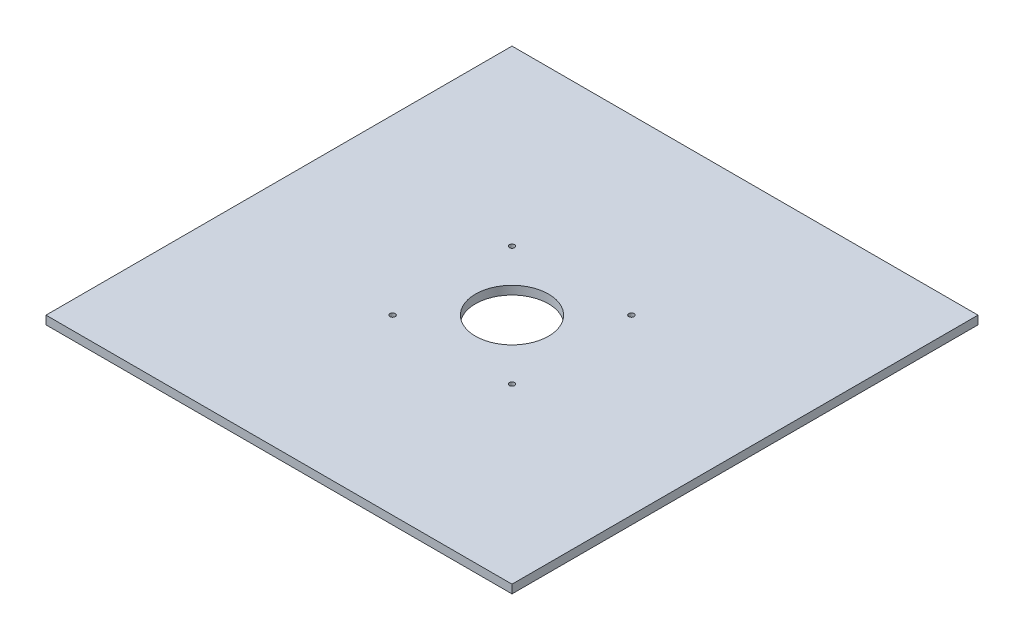
SolidWorks part; units mm, degrees
ref_plane "Front Plane" through (0, 0, 0) normal (0, 0, 1) x (1, 0, 0)
ref_plane "Top Plane" through (0, 0, 0) normal (0, 1, 0) x (1, 0, 0)
ref_plane "Right Plane" through (0, 0, 0) normal (1, 0, 0) x (0, 0, -1)
sketch "Sketch1" plane through (0, 0, 0) normal (0, 1, 0) x (1, 0, 0)
  line L1 (-175, -175) -> (175, -175)
  line L2 (-175, -175) -> (-175, 175)
  line L3 (-175, 175) -> (175, 175)
  line L4 (175, -175) -> (175, 175)
  line L5 (-175, -175) -> (175, 175) construction
  line L6 (-175, 175) -> (175, -175) construction
  point P0 (0, 0)
  dimension "D1" = 350
  dimension "D2" = 350
extrude "Boss-Extrude1" add sketch "Sketch1" along normal blind 6.35
sketch "Sketch2" plane through (0, 6.35, 0) normal (0, 1, 0) x (1, 0, 0)
  line L1 (-44.8437, -44.8437) -> (44.8437, -44.8437) construction
  line L2 (-44.8437, -44.8437) -> (-44.8437, 44.8437) construction
  line L3 (-44.8437, 44.8437) -> (44.8437, 44.8437) construction
  line L4 (44.8437, -44.8437) -> (44.8437, 44.8437) construction
  line L5 (-44.8437, -44.8437) -> (44.8437, 44.8437) construction
  line L6 (-44.8437, 44.8437) -> (44.8437, -44.8437) construction
  circle A0 centre (-44.8437, 44.8437) radius 1.9844
  circle A1 centre (44.8437, 44.8437) radius 1.9844
  circle A2 centre (-44.8437, -44.8437) radius 1.9844
  circle A3 centre (44.8437, -44.8437) radius 1.9844
  circle A4 centre (0, 0) radius 27.432
  point P0 (0, 0)
  dimension "D3" = 3.9688
  dimension "D4" = 54.864
  dimension "D1" = 89.6874
  dimension "D2" = 89.6874
extrude "Cut-Extrude1" cut sketch "Sketch2" against normal through all and the other way through all
